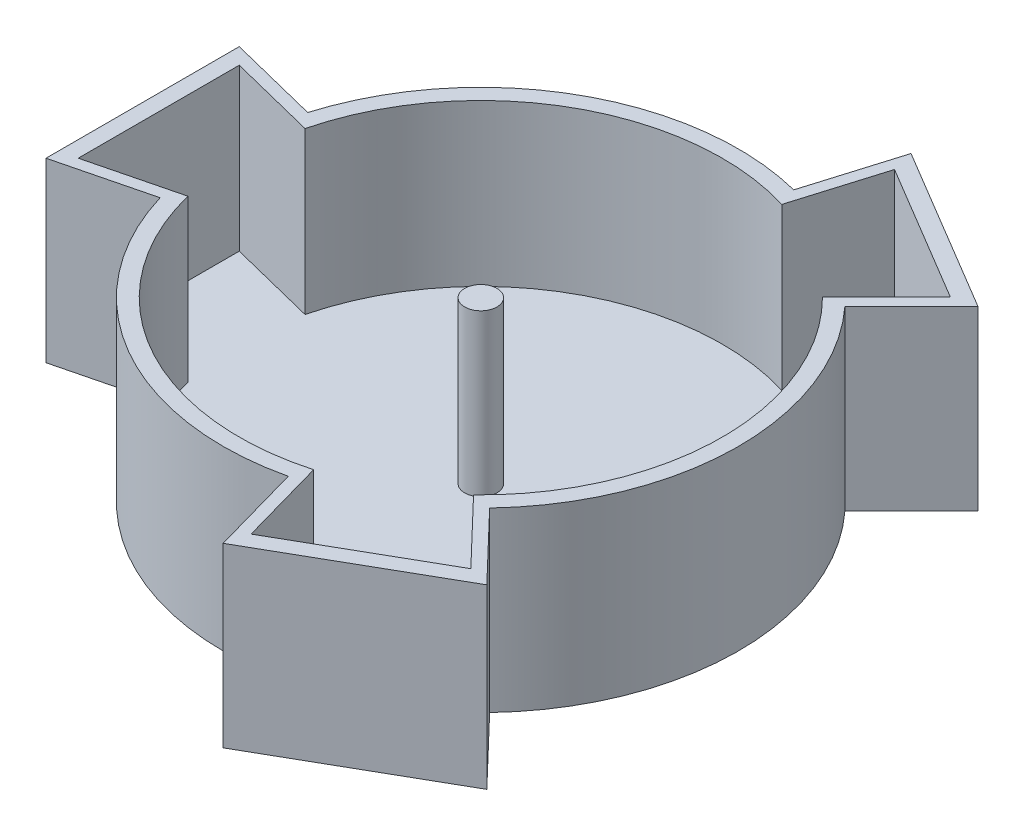
SolidWorks part; units mm, degrees
ref_plane "前视基准面" through (0, 0, 0) normal (0, 0, 1) x (1, 0, 0)
ref_plane "上视基准面" through (0, 0, 0) normal (0, 1, 0) x (1, 0, 0)
ref_plane "右视基准面" through (0, 0, 0) normal (1, 0, 0) x (0, 0, -1)
other "Configuration Table"
sketch "草图2" plane through (0, 0, 0) normal (0, 1, 0) x (1, 0, 0)
  line L5 (1.6383, -2.867) -> (1.6553, -2.867)
  line L8 (1.4686, 2.4623) -> (1.6822, 2.8203)
  line L9 (15.1155, 50.1343) -> (36.9298, 37.123)
  line L10 (-50.8, 12.7) -> (-50.8, -12.7)
  line L11 (14.1769, -50.4078) -> (36.2303, -37.806)
  line L12 (-53.34, 15.24) -> (-53.34, -15.24)
  line L13 (14.2352, 53.6169) -> (40.4124, 38.0033)
  line L14 (13.2317, -53.8733) -> (39.6958, -38.7512)
  line L15 (-50.8, 12.7) -> (-36.9624, 9.2406)
  line L16 (-50.8, -12.7) -> (-36.9624, -9.2406)
  line L17 (-53.34, -15.24) -> (-38.9376, -11.6394)
  line L18 (-53.34, 15.24) -> (-38.9376, 11.6394)
  line L19 (14.1769, -50.4078) -> (10.3152, -36.6771)
  line L20 (36.2303, -37.806) -> (26.3614, -27.5079)
  line L21 (13.2317, -53.8733) -> (9.2124, -39.5821)
  line L22 (39.6958, -38.7512) -> (29.4241, -28.0327)
  line L23 (36.9298, 37.123) -> (26.8704, 27.0109)
  line L24 (15.1155, 50.1343) -> (10.9982, 36.4781)
  line L25 (14.2352, 53.6169) -> (9.9498, 39.4032)
  line L26 (40.4124, 38.0033) -> (29.9423, 27.4785)
  line L28 (1.6822, 2.8203) -> (1.6553, 2.867)
  arc A0 (9.9498, 39.4032) -> (-38.9376, 11.6394) centre (0, 0) ccw
  circle A1 centre (0, 0) radius 38.1
  arc A2 (-38.9376, -11.6394) -> (9.2124, -39.5821) centre (0, 0) ccw
  arc A3 (29.4241, -28.0327) -> (29.9423, 27.4785) centre (0, 0) ccw
  point P20 (26.0227, 43.6287)
  point P22 (25.2036, -44.1069)
  point P27 (-53.34, 0)
  point P29 (27.3238, 45.8101)
  point P30 (26.4638, -46.3122)
  point P32 (-50.8, 0)
  dimension "D13" = 76.2
  dimension "D14" = 81.28
  dimension "D4" = 30.48
  dimension "D5" = 30.48
  dimension "D6" = 30.48
  dimension "D7" = 25.4
  dimension "D8" = 25.4
  dimension "D9" = 25.4
  dimension "D10" = 2.54
  dimension "D11" = 2.54
  dimension "D12" = 2.54
extrude "凸台-拉伸1" add sketch "草图2" along normal blind 25.4 contours L22 A3 L26 L13 L25 A0 L18 L12 L17 A2 L21 L14 A1 L20 L11 L19 L16 L10 L15 L24 L9 L23 region at (-46.4851, 0, -12.0545)
extrude "凸台-拉伸3" add sketch "草图2<4>" against normal blind 2.54 contours A1 | A1 L15 L10 L16 | A1 L19 L11 L20 | A1 L23 L9 L24 | L22 A3 L26 L13 L25 A0 L18 L12 L17 A2 L21 L14 A1 L20 L11 L19 L16 L10 L15 L24 L9 L23 region at (22.8345, 0, -38.2836) region at (0, 0, 0) region at (-44.5763, 0, 0) region at (22.1158, 0, 38.7032) region at (-46.4851, 0, -12.0545)
sketch "草图2<4>" plane through (0, 0, 0) normal (0, 1, 0) x (1, 0, 0) same geometry as "草图2"
sketch "草图3" plane through (0, 0, 0) normal (0, 1, 0) x (1, 0, 0)
  circle A0 centre (0, 0) radius 2.54
  dimension "D1" = 5.08
extrude "凸台-拉伸4" add sketch "草图3" along normal blind 25.4
